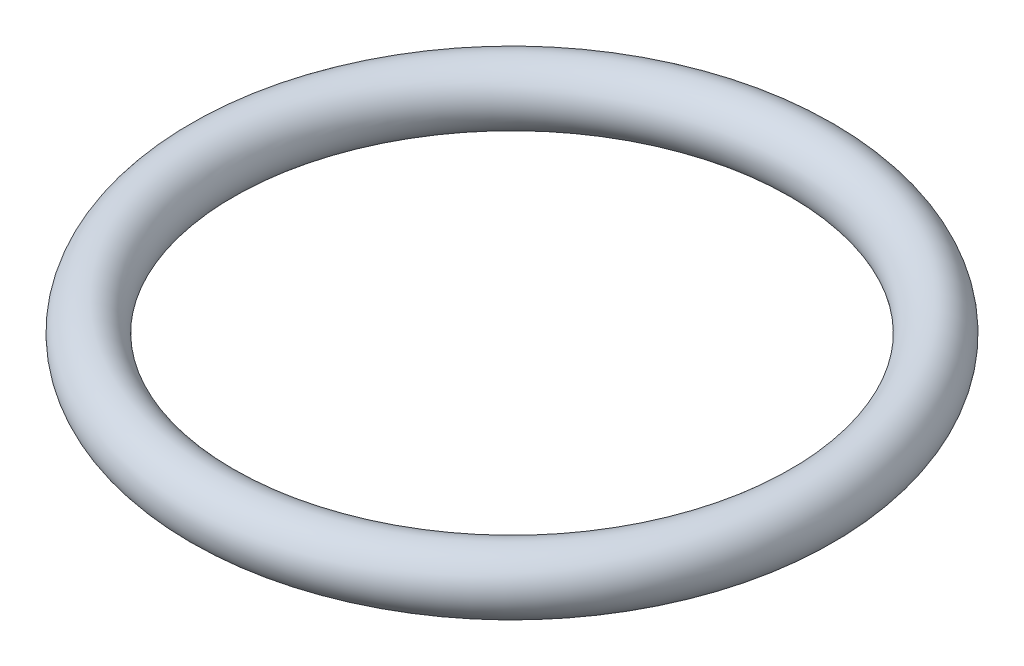
SolidWorks part; units mm, degrees
ref_plane "Front Plane" through (0, 0, 0) normal (0, 0, 1) x (1, 0, 0)
ref_plane "Top Plane" through (0, 0, 0) normal (0, 1, 0) x (1, 0, 0)
ref_plane "Right Plane" through (0, 0, 0) normal (1, 0, 0) x (0, 0, -1)
sketch "Sketch1" plane through (0, 0, 0) normal (0, 0, 1) x (1, 0, 0)
  line L0 (0, 37.1887) -> (0, -34.8951) construction
  circle A0 centre (5, 0) radius 0.5
revolve "Revolve1" add sketch "Sketch1" angle 360 about L0
ref_axis "Axis1" through (0, 37.1887, 0) along (0, -1, 0)
sketch "Sketch2" plane through (0, 0, 0) normal (1, 0, 0) x (0, 0, -1)
  point P2 (3.25, 0)
  point P3 (-3.25, 0)
